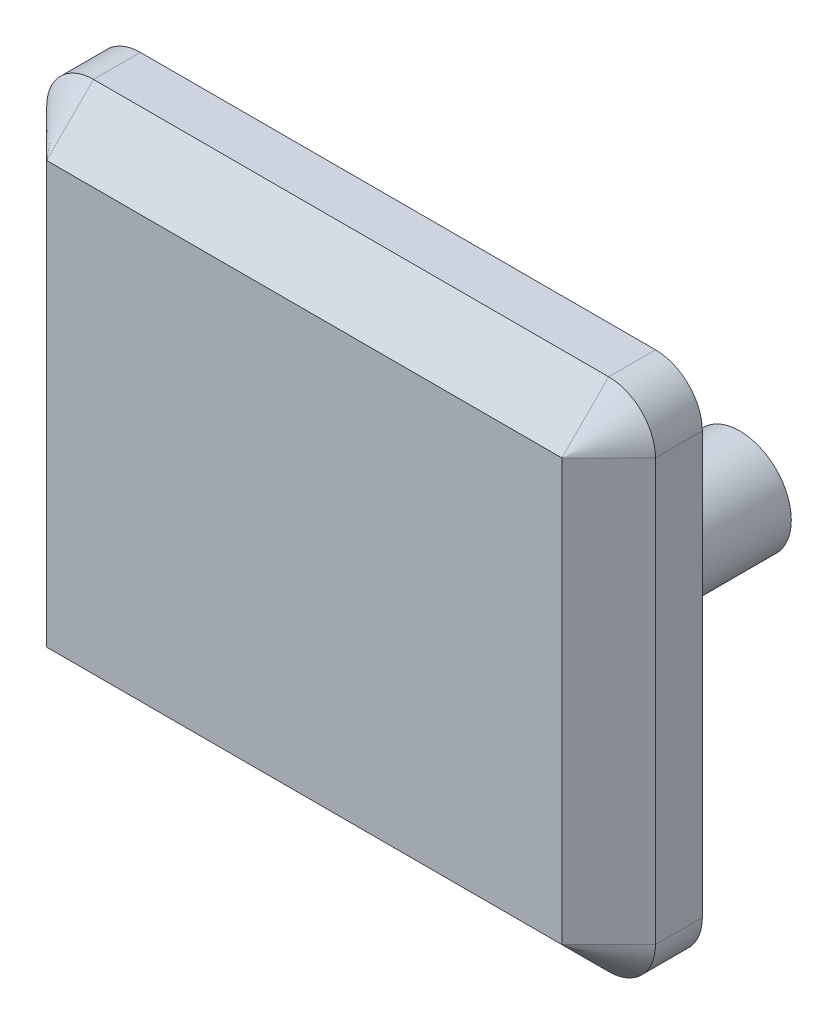
SolidWorks part; units mm, degrees
ref_plane "前视基准面" through (0, 0, 0) normal (0, 0, 1) x (1, 0, 0)
ref_plane "上视基准面" through (0, 0, 0) normal (0, 1, 0) x (1, 0, 0)
ref_plane "右视基准面" through (0, 0, 0) normal (1, 0, 0) x (0, 0, -1)
other "Configuration Table"
sketch "草图1" plane through (0, 0, 0) normal (0, 0, 1) x (1, 0, 0)
  line L1 (-7.2376, 4.5944) -> (-12.7376, 4.5944)
  line L2 (-6.7376, 5.0944) -> (-6.7376, 9.5944)
  line L3 (-7.2376, 10.0944) -> (-12.7376, 10.0944)
  line L4 (-13.2376, 5.0944) -> (-13.2376, 9.5944)
  arc A0 (-6.7376, 9.5944) -> (-7.2376, 10.0944) centre (-7.2376, 9.5944) ccw
  arc A1 (-12.7376, 10.0944) -> (-13.2376, 9.5944) centre (-12.7376, 9.5944) ccw
  arc A2 (-12.7376, 4.5944) -> (-13.2376, 5.0944) centre (-12.7376, 5.0944) cw
  arc A3 (-7.2376, 4.5944) -> (-6.7376, 5.0944) centre (-7.2376, 5.0944) ccw
  point P4 (-6.7376, 4.5944)
  point P5 (-13.2376, 10.0944)
  point P10 (-13.2376, 10.0944)
  point P13 (-13.2376, 4.5944)
  point P16 (-6.7376, 4.5944)
  dimension "D3" = 0.5
  dimension "D1" = 6.5
  dimension "D2" = 5.5
extrude "凸台-拉伸1" add sketch "草图1" along normal blind 1
chamfer "倒角1" distance 0.5 angle 45 8 edges at (-9.9876, 10.0944, 1) (-13.0912, 9.9479, 1) (-6.8841, 9.9479, 1) (-13.2376, 7.3444, 1) (-6.7376, 7.3444, 1) (-13.0912, 4.7408, 1) (-6.8841, 4.7408, 1) (-9.9876, 4.5944, 1)
sketch "草图2" plane through (0, 0, 0) normal (0, 0, -1) x (-1, 0, 0)
  circle A0 centre (11.7376, 7.3444) radius 0.55
  circle A1 centre (8.2376, 7.3444) radius 0.55
  dimension "D1" = 1.1
extrude "凸台-拉伸2" add sketch "草图2" along normal blind 1.9
